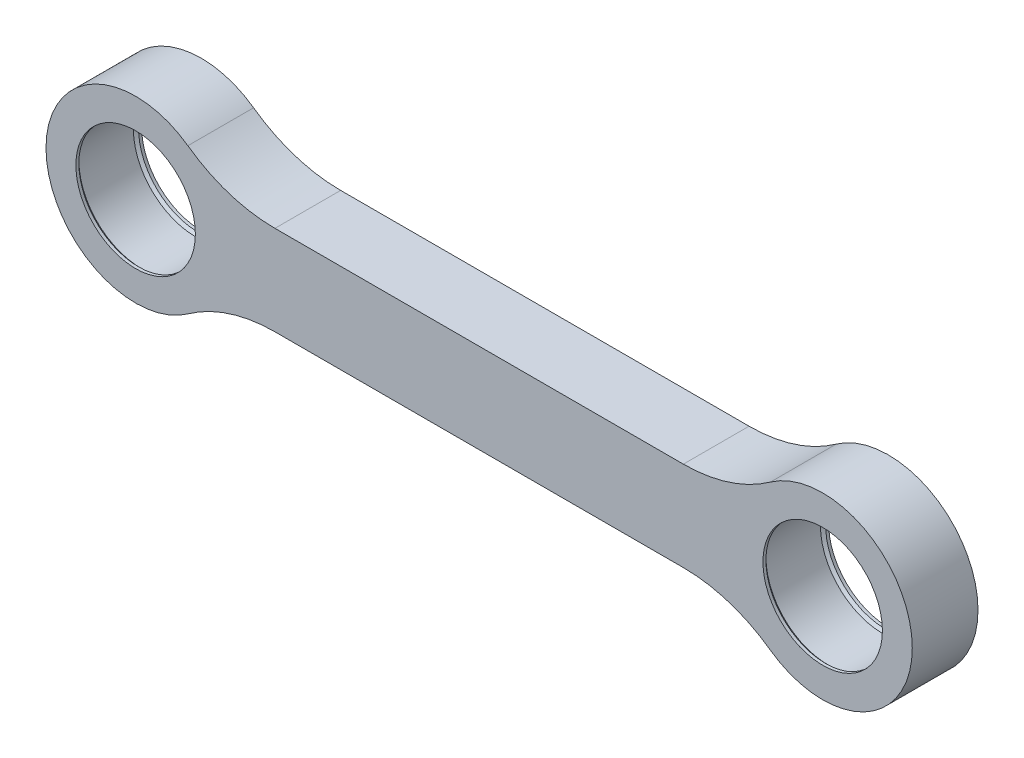
SolidWorks part; units mm, degrees
ref_plane "前视基准面" through (0, 0, 0) normal (0, 0, 1) x (1, 0, 0)
ref_plane "上视基准面" through (0, 0, 0) normal (0, 1, 0) x (1, 0, 0)
ref_plane "右视基准面" through (0, 0, 0) normal (1, 0, 0) x (0, 0, -1)
sketch "草图1" plane through (0, 0, 0) normal (0, 0, 1) x (1, 0, 0)
  line L1 (5, 3) -> (41, 3)
  line L2 (5, 3) -> (5, -3)
  line L3 (5, -3) -> (41, -3)
  line L4 (41, 3) -> (41, -3)
  line L5 (5, 3) -> (41, -3) construction
  line L6 (5, -3) -> (41, 3) construction
  circle A0 centre (0, 0) radius 4.175
  circle A1 centre (46, 0) radius 4.175
  circle A2 centre (0, 0) radius 6
  circle A3 centre (46, 0) radius 6
  circle A4 centre (0, 0) radius 4
  circle A5 centre (46, 0) radius 4
  point P5 (23, 0)
  dimension "D4" = 5
  dimension "D5" = 5
  dimension "D6" = 12
  dimension "D7" = 12
  dimension "D8" = 8.35
  dimension "D9" = 8
  dimension "D3" = 6
  dimension "D10" = 36
extrude "凸台-拉伸1" add sketch "草图1" along normal blind 4 and the other way blind 0.4 contours A0 A4 | L1 A2 L3 L2 A0 | A1 A5 | L3 A3 L1 L4 A1 | L1 L4 L3 L2 region at (4.8359, 0, 0) region at (47.5104, 5.637, 0) region at (-4.0569, 0, 0) region at (41.9431, 0, 0)
extrude "切除-拉伸1" cut sketch "草图1<3>" along normal blind 3.6 contours A0 A4 | A1 A5 region at (-4.0569, 0, 0) region at (41.9431, 0, 0)
sketch "草图1<3>" plane through (0, 0, 0) normal (0, 0, 1) x (1, 0, 0) same geometry as "草图1"
chamfer "倒角1" distance 0.2 angle 45 4 edges at (4, 0, 3.6) (50, 0, 3.6) (50, 0, 0) (4, 0, 0)
fillet "圆角1" radius 10 4 edges at (40.8038, -3, 1.8) (40.8038, 3, 1.8) (5.1962, 3, 1.8) (5.1962, -3, 1.8)
